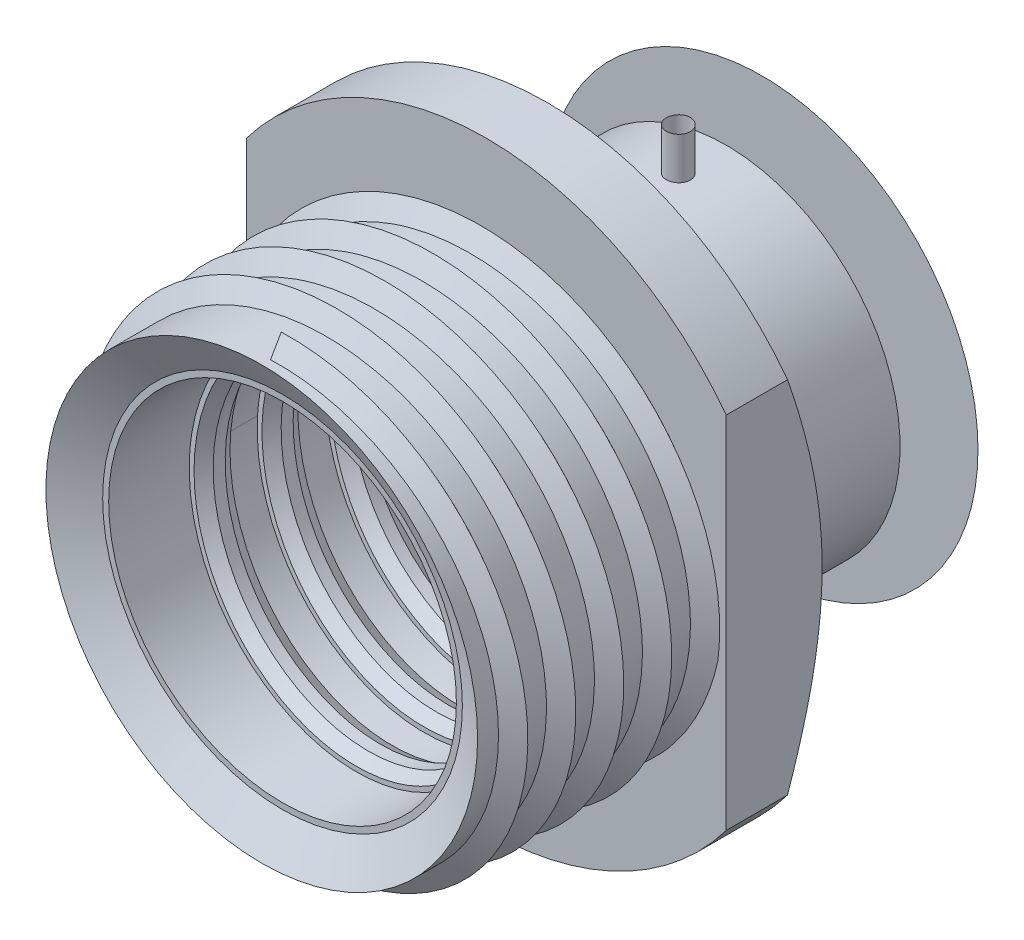
SolidWorks part; units mm, degrees
ref_plane "Спереди" through (0, 0, 0) normal (0, 0, 1) x (1, 0, 0)
ref_plane "Сверху" through (0, 0, 0) normal (0, 1, 0) x (1, 0, 0)
ref_plane "Справа" through (0, 0, 0) normal (1, 0, 0) x (0, 0, -1)
sketch "Эскиз1" plane through (0, 0, 0) normal (0, 0, 1) x (1, 0, 0)
  circle A0 centre (0, 0) radius 9
  dimension "D1" = 18
extrude "Бобышка-Вытянуть1" add sketch "Эскиз1" along normal blind 15
sketch "Эскиз2" plane through (0, 0, 0) normal (0, 0, -1) x (-1, 0, 0)
  circle A0 centre (0, 0) radius 7.25
  dimension "D1" = 14.5
extrude "Вырез-Вытянуть1" cut sketch "Эскиз2" against normal through all
sketch "Эскиз3" plane through (0, 0, 15) normal (0, 0, 1) x (1, 0, 0)
  circle A0 centre (0, 0) radius 7.5
  dimension "D1" = 15
extrude "Вырез-Вытянуть2" cut sketch "Эскиз3" against normal blind 2.5
ref_plane "Плоскость1" through (0, 0, 10.5) normal (0, 0, 1) x (1, 0, 0)
sketch "Эскиз4" plane through (0, 0, 10.5) normal (0, 0, 1) x (1, 0, 0)
  circle A0 centre (0, 0) radius 7.25 construction
  circle A1 centre (0, 0) radius 7.25
curve "Спираль1" pitch 2.8333 height 9.5 radius 7.25 centre (0, 0, 10.5) axis (0, 0, -1) start towards (0, 1, 0)
sketch "Эскиз5" plane through (0, 0, 0) normal (1, 0, 0) x (0, 0, -1)
  line L0 (-10.5, 8.25) -> (-10.5, -8.25) construction
  line L1 (-11.25, 7.25) -> (-9.75, 7.25)
  line L2 (-11.25, 7.25) -> (-11.25, 7.05)
  line L3 (-11.25, 7.05) -> (-10.75, 6.75)
  line L4 (-10.75, 6.75) -> (-10.25, 6.75)
  line L5 (-10.5, 7.25) -> (-10.5, 6.75) construction
  line L6 (-9.75, 7.05) -> (-10.25, 6.75)
  line L7 (-9.75, 7.25) -> (-9.75, 7.05)
  spline S0 degree 3 poles (-10.5, 7.25) (-10.4406, 7.25) (-10.3206, 6.8631) (-10.1416, 5.2126) (-9.9623, 2.7493) (-9.783, -0.1427) (-9.6038, -3.0125) (-9.4245, -5.4125) (-9.2453, -6.9686) (-9.066, -7.438) (-8.8868, -6.7476) (-8.7075, -5.005) (-8.5283, -2.482) (-8.3491, 0.428) (-8.1698, 3.2713) (-7.9906, 5.6045) (-7.8113, 7.0637) (-7.6321, 7.4216) (-7.4528, 6.6221) (-7.2736, 4.7901) (-7.0943, 2.2111) (-6.9151, -0.7126) (-6.7358, -3.5253) (-6.5566, -5.7882) (-6.3774, -7.1485) (-6.1981, -7.3942) (-6.0189, -6.4869) (-5.8396, -4.5681) (-5.6604, -1.9369) (-5.4811, 0.9962) (-5.3019, 3.774) (-5.1226, 5.9634) (-4.9434, 7.2228) (-4.7642, 7.356) (-4.5849, 6.3422) (-4.4057, 4.3394) (-4.2264, 1.6599) (-4.0472, -1.2783) (-3.8679, -4.0173) (-3.6887, -6.1298) (-3.5094, -7.2865) (-3.3302, -7.307) (-3.1509, -6.1881) (-2.9717, -4.1043) (-2.7925, -1.3805) (-2.6132, 1.5586) (-2.434, 4.2546) (-2.2547, 6.2872) (-2.0755, 7.3394) (-1.8962, 7.2472) (-1.717, 6.0249) (-1.5377, 3.8633) (-1.3584, 1.0984) (-1.1794, -1.8342) (-1.0594, -3.6075) (-1, -4.3691) knots 0 0 0 0 0.018868 0.037736 0.056604 0.075472 0.09434 0.113208 0.132075 0.150943 0.169811 0.188679 0.207547 0.226415 0.245283 0.264151 0.283019 0.301887 0.320755 0.339623 0.358491 0.377358 0.396226 0.415094 0.433962 0.45283 0.471698 0.490566 0.509434 0.528302 0.54717 0.566038 0.584906 0.603774 0.622642 0.641509 0.660377 0.679245 0.698113 0.716981 0.735849 0.754717 0.773585 0.792453 0.811321 0.830189 0.849057 0.867925 0.886792 0.90566 0.924528 0.943396 0.962264 0.981132 1 1 1 1 construction
  point P0 (-10.5, 7.25)
  point P1 (-10.5, 7.25)
  dimension "D1" = 1.5
  dimension "D2" = 0.5
  dimension "D3" = 0.5
  dimension "D4" = 0.2
sweep "По траектории1" add profiles "Эскиз5" path "Спираль1"
ref_plane "Плоскость2" through (0, 0, 0) normal (0, 0, 1) x (1, 0, 0)
sketch "Эскиз6" plane through (0, 0, 0) normal (0, 0, 1) x (1, 0, 0)
  line L0 (0, 12.5) -> (0, -12.5) construction
  line L1 (-10, 7.5) -> (-10, -7.5)
  line L2 (10, 7.5) -> (10, -7.5)
  circle A0 centre (0, 0) radius 9 construction
  circle A1 centre (0, 0) radius 9
  arc A2 (-10, -7.5) -> (10, -7.5) centre (0, 0) ccw
  arc A3 (10, 7.5) -> (-10, 7.5) centre (0, 0) ccw
  dimension "D1" = 25
  dimension "D2" = 20
extrude "Бобышка-Вытянуть2" add sketch "Эскиз6" along normal blind 4
ref_plane "Плоскость4" through (0, 0, 13) normal (0, 0, 1) x (1, 0, 0)
sketch "Эскиз8" plane through (0, 0, 13) normal (0, 0, 1) x (1, 0, 0)
  circle A0 centre (0, 0) radius 9 construction
  circle A1 centre (0, 0) radius 9
curve "Спираль2" pitch 2 height 10.5 radius 9 centre (0, 0, 13) axis (0, 0, -1) start towards (0, 1, 0)
sketch "Эскиз9" plane through (0, 0, 0) normal (1, 0, 0) x (0, 0, -1)
  line L0 (-13, 9) -> (-12, 9)
  line L2 (-13, 9) -> (-12.5523, 9.7755)
  line L3 (-12.5523, 9.7755) -> (-12, 9)
  line L4 (-13, 9.9) -> (-13, -9.9) construction
  line L5 (-4, 9) -> (-15, 9) construction
  dimension "D1" = 1
  dimension "D2" = 60
sweep "По траектории2" add profiles "Эскиз9" path "Спираль2"
sketch "Эскиз10" plane through (0, 0, 0) normal (0, 0, -1) x (-1, 0, 0)
  circle A0 centre (0, 0) radius 7.25 construction
  circle A1 centre (0, 0) radius 7.25
  circle A2 centre (0, 0) radius 9
  dimension "D1" = 18
extrude "Бобышка-Вытянуть3" add sketch "Эскиз10" along normal blind 6
sketch "Эскиз11" plane through (0, 0, 0) normal (1, 0, 0) x (0, 0, -1)
  line L0 (0, 9.9) -> (0, -9.9) construction
  line L1 (0, 0) -> (3.7177, 0) construction
  circle A0 centre (0.5, 5) radius 0.5
  circle A1 centre (0.5, -5) radius 0.5
  dimension "D1" = 1
  dimension "D2" = 0.5
  dimension "D3" = 5
extrude "Вырез-Вытянуть3" cut sketch "Эскиз11" against normal through all both and the other way through all
sketch "Эскиз12" plane through (0, 0, 0) normal (0, 1, 0) x (1, 0, 0)
  circle A0 centre (0, 4) radius 0.5
  dimension "D1" = 1
  dimension "D2" = 4
extrude "Вырез-Вытянуть4" cut sketch "Эскиз12" against normal through all both and the other way through all
sketch "Эскиз13" plane through (0, 0, -6) normal (0, 0, -1) x (-1, 0, 0)
  circle A0 centre (0, 0) radius 9 construction
  circle A1 centre (0, 0) radius 9
extrude "Бобышка-Вытянуть4" add sketch "Эскиз13" along normal blind 1.5
chamfer "Фаска1" distance 2.5 angle 30 2 edges at (0, 12.5, 0) (0, -12.5, 0) first distance on face at (0, 0, 0)
sketch "Эскиз14" plane through (0, 0, -6) normal (0, 0, 1) x (1, 0, 0)
  circle A0 centre (0, 0) radius 2.5
  dimension "D1" = 5
extrude "Бобышка-Вытянуть5" add sketch "Эскиз14" along normal blind 1
sketch "Эскиз15" plane through (0, 0, 15) normal (0, 0, 1) x (1, 0, 0)
  circle A0 centre (0, 0) radius 11.1764
extrude "Вырез-Вытянуть5" cut sketch "Эскиз15" against normal blind 1.5
chamfer "Фаска2" distance 1 angle 60 1 edges at (7.5, 0, 13.5) first distance on face at (7.5, 0, 12.5)
